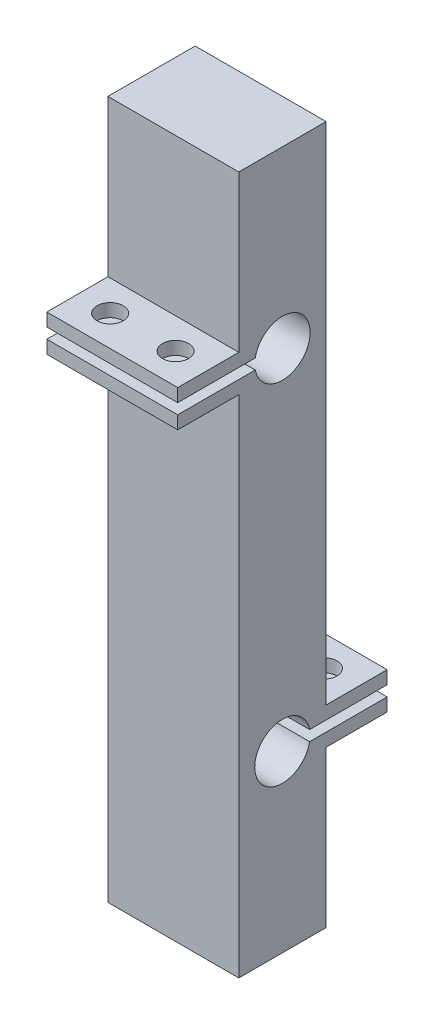
SolidWorks part; units mm, degrees
ref_plane "Front Plane" through (0, 0, 0) normal (0, 0, 1) x (1, 0, 0)
ref_plane "Top Plane" through (0, 0, 0) normal (0, 1, 0) x (1, 0, 0)
ref_plane "Right Plane" through (0, 0, 0) normal (1, 0, 0) x (0, 0, -1)
sketch "Sketch1" plane through (0, 0, 0) normal (0, 0, 1) x (1, 0, 0)
  line L1 (0, 0) -> (-15, 0)
  line L2 (0, 0) -> (0, 80)
  line L3 (0, 80) -> (-15, 80)
  line L4 (-15, 0) -> (-15, 80)
  dimension "D1" = 80
  dimension "D2" = 15
extrude "Boss-Extrude1" add sketch "Sketch1" along normal blind 10
sketch "Sketch3" plane through (0, 0, 0) normal (1, 0, 0) x (0, 0, -1)
  line L0 (-5, 80) -> (-5, 0) construction
  line L1 (-10, 80) -> (0, 80) construction
  line L2 (-10, 0) -> (0, 0) construction
  line L3 (-5, 0) -> (-10, 20) construction
  line L4 (-10, 0) -> (-10, 80) construction
  line L5 (-10, 20) -> (-5, 40) construction
  line L6 (-5, 40) -> (-10, 60) construction
  line L7 (-10, 60) -> (-5, 80) construction
  line L8 (-10, 60) -> (0, 60) construction
  line L9 (0, 0) -> (0, 80) construction
  line L10 (-10, 20) -> (0, 20) construction
  circle A0 centre (-5, 60) radius 3.175
  circle A1 centre (-5, 20) radius 3.175
  point P8 (0, 0)
  point P20 (-5, 13.5004)
  dimension "D1" = 6.35
extrude "Cut-Extrude1" cut sketch "Sketch3" against normal blind 12.7
sketch "Sketch6" plane through (0, 0, 0) normal (1, 0, 0) x (0, 0, -1)
  line L0 (-10, 62.1) -> (-10, 57.9)
  line L9 (-10, 57.9) -> (-17, 57.9)
  line L11 (-10, 62.1) -> (-17, 62.1)
  line L12 (-17, 57.9) -> (-17, 62.1)
  line L13 (-10, 60) -> (-17, 62.1) construction
  line L14 (-10, 60) -> (-17, 57.9) construction
  line L16 (7, 17.9) -> (0, 17.9)
  line L17 (7, 17.9) -> (7, 22.1)
  line L18 (7, 22.1) -> (0, 22.1)
  line L20 (7, 17.9) -> (0, 20) construction
  line L21 (7, 22.1) -> (0, 20) construction
  line L22 (0, 22.1) -> (0, 17.9)
  line L23 (0, 0) -> (0, 80) construction
  point P0 (-10, 60)
  point P2 (0, 20)
  dimension "D1" = 7
  dimension "D2" = 4.2
extrude "Boss-Extrude3" add sketch "Sketch6" against normal up to surface (15 mm away) up to face at (-15, 40, 5)
sketch "Sketch5" plane through (0, 0, 0) normal (1, 0, 0) x (0, 0, -1)
  line L0 (-10, 60) -> (0, 60) construction
  line L1 (-17, 59.4) -> (-8.1178, 59.4)
  line L3 (-17, 60.6) -> (-8.1178, 60.6)
  line L5 (-17, 62.1) -> (-17, 57.9) construction
  line L6 (-5, 20) -> (-1.825, 20) construction
  line L7 (-17, 60.6) -> (-17, 59.4)
  line L8 (7, 20.6) -> (7, 19.4)
  line L9 (7, 19.4) -> (-1.8822, 19.4)
  line L11 (7, 20.6) -> (-1.8822, 20.6)
  line L13 (-1.8822, 20.6) -> (-5, 20) construction
  line L14 (-5, 20) -> (-1.8822, 19.4) construction
  arc A0 (-8.1178, 59.4) -> (-8.1178, 60.6) centre (-5, 60) cw
  circle A1 centre (-5, 60) radius 3.175 construction
  arc A2 (-1.8822, 20.6) -> (-1.8822, 19.4) centre (-5, 20) cw
  circle A3 centre (-5, 20) radius 3.175 construction
  circle A4 centre (-5, 60) radius 3.175 construction
  circle A5 centre (-5, 60) radius 3.175 construction
  circle A6 centre (-5, 20) radius 3.175 construction
  point P0 (-10, 60)
  point P2 (0, 20)
  dimension "D2" = 1.2
extrude "Cut-Extrude2" cut sketch "Sketch5" against normal up to surface (15 mm away) up to face at (-15, 40, 5)
sketch "Sketch7" plane through (-15, 0, 0) normal (-1, 0, 0) x (0, 0, 1)
  line L0 (8.1178, 59.4) -> (8.2178, 59.4)
  line L1 (8.1178, 59.4) -> (17, 59.4) construction
  line L2 (8.2178, 59.4) -> (8.2178, 60.6)
  line L3 (17, 60.6) -> (8.1178, 60.6) construction
  line L4 (8.2178, 60.6) -> (8.1178, 60.6)
  line L5 (1.8822, 19.4) -> (1.7822, 19.4)
  line L6 (-7, 19.4) -> (1.8822, 19.4) construction
  line L7 (1.7822, 19.4) -> (1.7822, 20.6)
  line L8 (1.8822, 20.6) -> (-7, 20.6) construction
  line L9 (1.7822, 20.6) -> (1.8822, 20.6)
  arc A0 (8.1178, 59.4) -> (8.1178, 60.6) centre (5, 60) ccw construction
  arc A1 (8.1178, 59.4) -> (8.1178, 60.6) centre (5, 60) ccw
  arc A2 (1.8822, 20.6) -> (1.8822, 19.4) centre (5, 20) ccw construction
  arc A3 (1.8822, 20.6) -> (1.8822, 19.4) centre (5, 20) ccw
  dimension "D1" = 0.1
extrude "Boss-Extrude2" add sketch "Sketch7" against normal up to surface (2.3 mm away) up to face at (-12.7, 60, 5)
sketch "Sketch8" plane through (0, 62.1, 0) normal (0, 1, 0) x (1, 0, 0)
  line L0 (-15, -13.5) -> (0, -13.5) construction
  line L1 (-15, -17) -> (-15, -10) construction
  line L2 (0, -10) -> (0, -17) construction
  line L3 (-15, -13.5) -> (-11.25, -17) construction
  line L4 (-15, -17) -> (0, -17) construction
  line L5 (-11.25, -17) -> (-7.5, -13.5) construction
  line L6 (-7.5, -13.5) -> (-3.75, -17) construction
  line L7 (-3.75, -17) -> (0, -13.5) construction
  line L8 (-11.25, -17) -> (-11.25, -13.5) construction
  line L9 (-3.75, -17) -> (-3.75, -13.5) construction
  circle A0 centre (-11.25, -13.5) radius 1.5
  circle A1 centre (-3.75, -13.5) radius 1.5
  dimension "D1" = 3
extrude "Cut-Extrude3" cut sketch "Sketch8" against normal up to surface (4.2 mm away) up to face at (-7.5, 57.9, 13.5)
sketch "Sketch9" plane through (0, 22.1, 0) normal (0, 1, 0) x (1, 0, 0)
  line L0 (-15, 3.5) -> (0, 3.5) construction
  line L1 (-15, 0) -> (-15, 7) construction
  line L2 (0, 7) -> (0, 0) construction
  line L3 (-15, 3.5) -> (-11.25, 7) construction
  line L4 (-15, 7) -> (0, 7) construction
  line L5 (-11.25, 7) -> (-7.5, 3.5) construction
  line L6 (-7.5, 3.5) -> (-3.75, 7) construction
  line L7 (-3.75, 7) -> (0, 3.5) construction
  line L8 (-11.25, 7) -> (-11.25, 3.5) construction
  line L9 (-3.75, 7) -> (-3.75, 3.5) construction
  circle A0 centre (-11.25, 3.5) radius 1.5
  circle A1 centre (-3.75, 3.5) radius 1.5
  dimension "D1" = 3
extrude "Cut-Extrude4" cut sketch "Sketch9" against normal up to surface (4.2 mm away) up to face at (-7.5, 17.9, -3.5)
